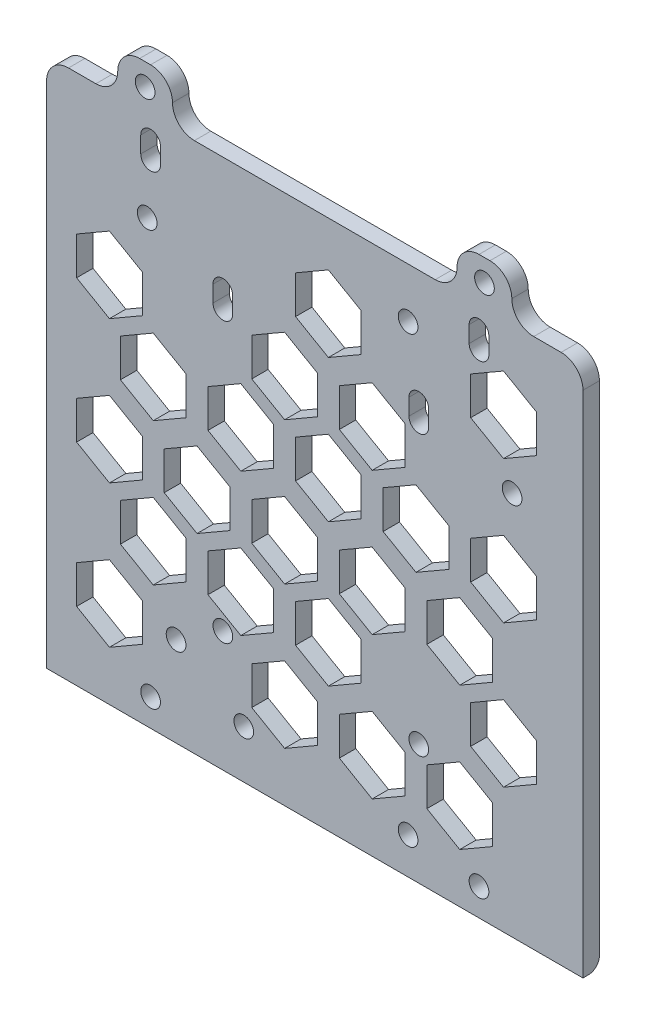
SolidWorks part; units mm, degrees
material "PLA 100% Infill"
ref_plane "Front Plane" through (0, 0, 0) normal (0, 0, 1) x (1, 0, 0)
ref_plane "Top Plane" through (0, 0, 0) normal (0, 1, 0) x (1, 0, 0)
ref_plane "Right Plane" through (0, 0, 0) normal (1, 0, 0) x (0, 0, -1)
sketch "Sketch1" plane through (0, 0, 0) normal (0, 0, 1) x (1, 0, 0)
  line L0 (-49, 97) -> (-49, 0) construction
  line L1 (0, 0) -> (-98, 0)
  line L2 (0, 0) -> (0, 97)
  line L3 (0, 97) -> (-98, 97)
  line L4 (-98, 0) -> (-98, 97)
  line L5 (-80, 101) -> (-18, 101) construction
  line L6 (-98, 97) -> (-75, 97)
  line L8 (-85, 105) -> (-75, 105)
  line L9 (-75, 97) -> (-75, 105)
  line L10 (0, 97) -> (-23, 97)
  line L12 (-13, 105) -> (-23, 105)
  line L13 (-23, 97) -> (-23, 105)
  line L14 (-80, 105) -> (-80, 101) construction
  line L15 (-85, 105) -> (-85, 97)
  line L16 (-80.8, 93) -> (-80.8, 90)
  line L17 (-13, 105) -> (-13, 97)
  line L18 (-18, 105) -> (-18, 101) construction
  line L19 (-77.2, 90) -> (-77.2, 93)
  line L20 (-20.8, 90) -> (-20.8, 93)
  line L21 (-17.2, 93) -> (-17.2, 90)
  line L22 (-19, 91.5) -> (-19, 5) construction
  line L23 (-30, 22) -> (-65.8, 22) construction
  line L24 (-65.8, 76) -> (-65.8, 22) construction
  line L25 (-30, 76) -> (-30, 22) construction
  line L26 (-67.6, 76) -> (-67.6, 73)
  line L27 (-64, 76) -> (-64, 73)
  line L28 (-31.8, 76) -> (-31.8, 73)
  line L29 (-28.2, 76) -> (-28.2, 73)
  circle A0 centre (-79, 5) radius 1.8
  circle A1 centre (-19, 5) radius 1.8
  circle A2 centre (-19, 91.5) radius 1.8
  circle A3 centre (-79, 91.5) radius 1.8
  circle A4 centre (-80, 101) radius 1.8
  circle A5 centre (-18, 101) radius 1.8
  arc A6 (-80.8, 90) -> (-77.2, 90) centre (-79, 90) ccw
  arc A7 (-77.2, 93) -> (-80.8, 93) centre (-79, 93) ccw
  arc A8 (-17.2, 90) -> (-20.8, 90) centre (-19, 90) cw
  arc A9 (-20.8, 93) -> (-17.2, 93) centre (-19, 93) cw
  circle A10 centre (-30, 22) radius 1.8
  circle A11 centre (-65.8, 22) radius 1.8
  circle A12 centre (-65.8, 76) radius 1.8
  circle A13 centre (-30, 76) radius 1.8
  circle A14 centre (-65.8, 73) radius 1.8
  circle A15 centre (-30, 73) radius 1.8
  dimension "D5" = 3.6
  dimension "D8" = 86.5
  dimension "D9" = 10
  dimension "D10" = 8
  dimension "D4" = 5
  dimension "D11" = 62
  dimension "D12" = 62
  dimension "D15" = 4
  dimension "D16" = 60
  dimension "D17" = 3.6
  dimension "D1" = 98
  dimension "D2" = 97
  dimension "D3" = 60
  dimension "D13" = 1.5
  dimension "D14" = 3
  dimension "D18" = 35.8
  dimension "D19" = 30
  dimension "D20" = 22
  dimension "D22" = 3
  dimension "D23" = 54
  dimension "D6" = 2
  dimension "D7" = 2
  dimension "D21" = 2
extrude "Boss-Extrude1" add sketch "Sketch1" along normal blind 3 contours L3 L9 L8 A4 | L4 L1 L2 L3 A3 A2 A1 A0 | L13 L3 L12 A5 region at (-49.0073, 48.3433, 0) region at (-18, 97.1281, 0) region at (-84.8719, 101, 0)
fillet "Fillet1" radius 4 10 edges at (0, 97, 1.5) (-13, 97, 1.5) (-13, 105, 1.5) (-23, 105, 1.5) (-23, 97, 1.5) (-75, 97, 1.5) (-75, 105, 1.5) (-98, 97, 1.5) (-85, 105, 1.5) (-85, 97, 1.5)
fillet "Fillet2" radius 2 1 edges at (-49, 0, 0)
sketch "Sketch3" plane through (0, 0, 3) normal (0, 0, 1) x (1, 0, 0)
  line L0 (-98, 0) -> (-98, 93) construction
  line L1 (-80.5172, 12.537) -> (-80.5172, 19.4652)
  line L2 (-80.5172, 19.4652) -> (-86.5172, 22.9293)
  line L3 (-86.5172, 22.9293) -> (-92.5172, 19.4652)
  line L4 (-92.5172, 19.4652) -> (-92.5172, 12.537)
  line L5 (-92.5172, 12.537) -> (-86.5172, 9.0729)
  line L6 (-86.5172, 9.0729) -> (-80.5172, 12.537)
  line L14 (-72.5172, 26.3934) -> (-72.5172, 33.3216)
  line L15 (-72.5172, 33.3216) -> (-78.5172, 36.7857)
  line L16 (-78.5172, 36.7857) -> (-84.5172, 33.3216)
  line L17 (-84.5172, 33.3216) -> (-84.5172, 26.3934)
  line L18 (-84.5172, 26.3934) -> (-78.5172, 22.9293)
  line L19 (-78.5172, 22.9293) -> (-72.5172, 26.3934)
  line L25 (-56.5172, 26.3934) -> (-56.5172, 33.3216)
  line L26 (-56.5172, 33.3216) -> (-62.5172, 36.7857)
  line L27 (-62.5172, 36.7857) -> (-68.5172, 33.3216)
  line L28 (-68.5172, 33.3216) -> (-68.5172, 26.3934)
  line L29 (-68.5172, 26.3934) -> (-62.5172, 22.9293)
  line L30 (-62.5172, 22.9293) -> (-56.5172, 26.3934)
  line L31 (-48.5172, 12.537) -> (-48.5172, 19.4652)
  line L32 (-48.5172, 19.4652) -> (-54.5172, 22.9293)
  line L33 (-54.5172, 22.9293) -> (-60.5172, 19.4652)
  line L34 (-60.5172, 19.4652) -> (-60.5172, 12.537)
  line L35 (-60.5172, 12.537) -> (-54.5172, 9.0729)
  line L36 (-54.5172, 9.0729) -> (-48.5172, 12.537)
  line L37 (-40.5172, 26.3934) -> (-40.5172, 33.3216)
  line L38 (-40.5172, 33.3216) -> (-46.5172, 36.7857)
  line L39 (-46.5172, 36.7857) -> (-52.5172, 33.3216)
  line L40 (-52.5172, 33.3216) -> (-52.5172, 26.3934)
  line L41 (-52.5172, 26.3934) -> (-46.5172, 22.9293)
  line L42 (-46.5172, 22.9293) -> (-40.5172, 26.3934)
  line L43 (-32.5172, 12.537) -> (-32.5172, 19.4652)
  line L44 (-32.5172, 19.4652) -> (-38.5172, 22.9293)
  line L45 (-38.5172, 22.9293) -> (-44.5172, 19.4652)
  line L46 (-44.5172, 19.4652) -> (-44.5172, 12.537)
  line L47 (-44.5172, 12.537) -> (-38.5172, 9.0729)
  line L48 (-38.5172, 9.0729) -> (-32.5172, 12.537)
  line L55 (-16.5172, 12.537) -> (-16.5172, 19.4652)
  line L56 (-16.5172, 19.4652) -> (-22.5172, 22.9293)
  line L57 (-22.5172, 22.9293) -> (-28.5172, 19.4652)
  line L58 (-28.5172, 19.4652) -> (-28.5172, 12.537)
  line L59 (-28.5172, 12.537) -> (-22.5172, 9.0729)
  line L60 (-22.5172, 9.0729) -> (-16.5172, 12.537)
  line L61 (-8.5172, 26.3934) -> (-8.5172, 33.3216)
  line L62 (-8.5172, 33.3216) -> (-14.5172, 36.7857)
  line L63 (-14.5172, 36.7857) -> (-20.5172, 33.3216)
  line L64 (-20.5172, 33.3216) -> (-20.5172, 26.3934)
  line L65 (-20.5172, 26.3934) -> (-14.5172, 22.9293)
  line L66 (-14.5172, 22.9293) -> (-8.5172, 26.3934)
  line L67 (-64.5172, 38.537) -> (-64.5172, 45.4652)
  line L68 (-64.5172, 45.4652) -> (-70.5172, 48.9293)
  line L69 (-70.5172, 48.9293) -> (-76.5172, 45.4652)
  line L70 (-76.5172, 45.4652) -> (-76.5172, 38.537)
  line L71 (-76.5172, 38.537) -> (-70.5172, 35.0729)
  line L72 (-70.5172, 35.0729) -> (-64.5172, 38.537)
  line L73 (-56.5172, 52.3934) -> (-56.5172, 59.3216)
  line L74 (-56.5172, 59.3216) -> (-62.5172, 62.7857)
  line L75 (-62.5172, 62.7857) -> (-68.5172, 59.3216)
  line L76 (-68.5172, 59.3216) -> (-68.5172, 52.3934)
  line L77 (-68.5172, 52.3934) -> (-62.5172, 48.9293)
  line L78 (-62.5172, 48.9293) -> (-56.5172, 52.3934)
  line L79 (-48.5172, 38.537) -> (-48.5172, 45.4652)
  line L80 (-48.5172, 45.4652) -> (-54.5172, 48.9293)
  line L81 (-54.5172, 48.9293) -> (-60.5172, 45.4652)
  line L82 (-60.5172, 45.4652) -> (-60.5172, 38.537)
  line L83 (-60.5172, 38.537) -> (-54.5172, 35.0729)
  line L84 (-54.5172, 35.0729) -> (-48.5172, 38.537)
  line L85 (-40.5172, 52.3934) -> (-40.5172, 59.3216)
  line L86 (-40.5172, 59.3216) -> (-46.5172, 62.7857)
  line L87 (-46.5172, 62.7857) -> (-52.5172, 59.3216)
  line L88 (-52.5172, 59.3216) -> (-52.5172, 52.3934)
  line L89 (-52.5172, 52.3934) -> (-46.5172, 48.9293)
  line L90 (-46.5172, 48.9293) -> (-40.5172, 52.3934)
  line L91 (-32.5172, 38.537) -> (-32.5172, 45.4652)
  line L92 (-32.5172, 45.4652) -> (-38.5172, 48.9293)
  line L93 (-38.5172, 48.9293) -> (-44.5172, 45.4652)
  line L94 (-44.5172, 45.4652) -> (-44.5172, 38.537)
  line L95 (-44.5172, 38.537) -> (-38.5172, 35.0729)
  line L96 (-38.5172, 35.0729) -> (-32.5172, 38.537)
  line L97 (-24.5172, 52.3934) -> (-24.5172, 59.3216)
  line L98 (-24.5172, 59.3216) -> (-30.5172, 62.7857)
  line L99 (-30.5172, 62.7857) -> (-36.5172, 59.3216)
  line L100 (-36.5172, 59.3216) -> (-36.5172, 52.3934)
  line L101 (-36.5172, 52.3934) -> (-30.5172, 48.9293)
  line L102 (-30.5172, 48.9293) -> (-24.5172, 52.3934)
  line L103 (-16.5172, 38.537) -> (-16.5172, 45.4652)
  line L104 (-16.5172, 45.4652) -> (-22.5172, 48.9293)
  line L105 (-22.5172, 48.9293) -> (-28.5172, 45.4652)
  line L106 (-28.5172, 45.4652) -> (-28.5172, 38.537)
  line L107 (-28.5172, 38.537) -> (-22.5172, 35.0729)
  line L108 (-22.5172, 35.0729) -> (-16.5172, 38.537)
  line L109 (-8.5172, 52.3934) -> (-8.5172, 59.3216)
  line L110 (-8.5172, 59.3216) -> (-14.5172, 62.7857)
  line L111 (-14.5172, 62.7857) -> (-20.5172, 59.3216)
  line L112 (-20.5172, 59.3216) -> (-20.5172, 52.3934)
  line L113 (-20.5172, 52.3934) -> (-14.5172, 48.9293)
  line L114 (-14.5172, 48.9293) -> (-8.5172, 52.3934)
  line L127 (-48.5172, 64.537) -> (-48.5172, 71.4652)
  line L128 (-48.5172, 71.4652) -> (-54.5172, 74.9293)
  line L129 (-54.5172, 74.9293) -> (-60.5172, 71.4652)
  line L130 (-60.5172, 71.4652) -> (-60.5172, 64.537)
  line L131 (-60.5172, 64.537) -> (-54.5172, 61.0729)
  line L132 (-54.5172, 61.0729) -> (-48.5172, 64.537)
  line L133 (-40.5172, 78.3934) -> (-40.5172, 85.3216)
  line L134 (-40.5172, 85.3216) -> (-46.5172, 88.7857)
  line L135 (-46.5172, 88.7857) -> (-52.5172, 85.3216)
  line L136 (-52.5172, 85.3216) -> (-52.5172, 78.3934)
  line L137 (-52.5172, 78.3934) -> (-46.5172, 74.9293)
  line L138 (-46.5172, 74.9293) -> (-40.5172, 78.3934)
  line L139 (-32.5172, 64.537) -> (-32.5172, 71.4652)
  line L140 (-32.5172, 71.4652) -> (-38.5172, 74.9293)
  line L141 (-38.5172, 74.9293) -> (-44.5172, 71.4652)
  line L142 (-44.5172, 71.4652) -> (-44.5172, 64.537)
  line L143 (-44.5172, 64.537) -> (-38.5172, 61.0729)
  line L144 (-38.5172, 61.0729) -> (-32.5172, 64.537)
  line L157 (-8.5172, 78.3934) -> (-8.5172, 85.3216)
  line L158 (-8.5172, 85.3216) -> (-14.5172, 88.7857)
  line L159 (-14.5172, 88.7857) -> (-20.5172, 85.3216)
  line L160 (-20.5172, 85.3216) -> (-20.5172, 78.3934)
  line L161 (-20.5172, 78.3934) -> (-14.5172, 74.9293)
  line L162 (-14.5172, 74.9293) -> (-8.5172, 78.3934)
  line L163 (-80.5172, 38.537) -> (-80.5172, 45.4652)
  line L164 (-80.5172, 45.4652) -> (-86.5172, 48.9293)
  line L165 (-86.5172, 48.9293) -> (-92.5172, 45.4652)
  line L166 (-92.5172, 45.4652) -> (-92.5172, 38.537)
  line L167 (-92.5172, 38.537) -> (-86.5172, 35.0729)
  line L168 (-86.5172, 35.0729) -> (-80.5172, 38.537)
  line L169 (-72.5172, 52.3934) -> (-72.5172, 59.3216)
  line L170 (-72.5172, 59.3216) -> (-78.5172, 62.7857)
  line L171 (-78.5172, 62.7857) -> (-84.5172, 59.3216)
  line L172 (-84.5172, 59.3216) -> (-84.5172, 52.3934)
  line L173 (-84.5172, 52.3934) -> (-78.5172, 48.9293)
  line L174 (-78.5172, 48.9293) -> (-72.5172, 52.3934)
  line L175 (-80.5172, 64.537) -> (-80.5172, 71.4652)
  line L176 (-80.5172, 71.4652) -> (-86.5172, 74.9293)
  line L177 (-86.5172, 74.9293) -> (-92.5172, 71.4652)
  line L178 (-92.5172, 71.4652) -> (-92.5172, 64.537)
  line L179 (-92.5172, 64.537) -> (-86.5172, 61.0729)
  line L180 (-86.5172, 61.0729) -> (-80.5172, 64.537)
  line L187 (-56.5172, 85.3216) -> (-62.5172, 88.7857) [skipped]
  line L188 (-68.5172, 78.3934) -> (-62.5172, 74.9293) [skipped]
  line L189 (-64.5172, 71.4652) -> (-70.5172, 74.9293) [skipped]
  line L190 (-76.5172, 64.537) -> (-70.5172, 61.0729) [skipped]
  line L191 (-70.5172, 61.0729) -> (-64.5172, 64.537) [skipped]
  line L192 (-64.5172, 64.537) -> (-64.5172, 71.4652) [skipped]
  line L193 (-70.5172, 74.9293) -> (-76.5172, 71.4652) [skipped]
  line L194 (-76.5172, 71.4652) -> (-76.5172, 64.537) [skipped]
  line L195 (-62.5172, 88.7857) -> (-68.5172, 85.3216) [skipped]
  line L196 (-72.5172, 78.3934) -> (-72.5172, 85.3216) [skipped]
  line L197 (-84.5172, 85.3216) -> (-84.5172, 78.3934) [skipped]
  line L198 (-78.5172, 88.7857) -> (-84.5172, 85.3216) [skipped]
  line L199 (-72.5172, 85.3216) -> (-78.5172, 88.7857) [skipped]
  line L200 (-84.5172, 78.3934) -> (-78.5172, 74.9293) [skipped]
  line L201 (-78.5172, 74.9293) -> (-72.5172, 78.3934) [skipped]
  line L202 (-68.5172, 85.3216) -> (-68.5172, 78.3934) [skipped]
  line L203 (-62.5172, 74.9293) -> (-56.5172, 78.3934) [skipped]
  line L204 (-56.5172, 78.3934) -> (-56.5172, 85.3216) [skipped]
  line L205 (-36.5172, 78.3934) -> (-30.5172, 74.9293) [skipped]
  line L206 (-24.5172, 78.3934) -> (-24.5172, 85.3216) [skipped]
  line L207 (-30.5172, 88.7857) -> (-36.5172, 85.3216) [skipped]
  line L208 (-36.5172, 85.3216) -> (-36.5172, 78.3934) [skipped]
  line L209 (-24.5172, 85.3216) -> (-30.5172, 88.7857) [skipped]
  line L210 (-30.5172, 74.9293) -> (-24.5172, 78.3934) [skipped]
  line L211 (-64.5172, 19.4652) -> (-70.5172, 22.9293) [skipped]
  line L212 (-64.5172, 12.537) -> (-64.5172, 19.4652) [skipped]
  line L213 (-36.5172, 26.3934) -> (-30.5172, 22.9293) [skipped]
  line L214 (-30.5172, 22.9293) -> (-24.5172, 26.3934) [skipped]
  line L215 (-24.5172, 23.3102) -> (-24.5172, 33.3216) [skipped]
  line L216 (-24.5172, 33.3216) -> (-30.5172, 36.7857) [skipped]
  line L217 (-30.5172, 36.7857) -> (-36.5172, 33.3216) [skipped]
  line L218 (-36.5172, 33.3216) -> (-36.5172, 26.3934) [skipped]
  line L219 (-70.5172, 9.0729) -> (-64.5172, 12.537) [skipped]
  line L220 (-76.5172, 12.537) -> (-70.5172, 9.0729) [skipped]
  line L221 (-76.5172, 19.4652) -> (-76.5172, 12.537) [skipped]
  line L222 (-70.5172, 22.9293) -> (-76.5172, 19.4652) [skipped]
  line L223 (-22.5172, 74.9293) -> (-28.5172, 71.4652) [skipped]
  line L224 (-28.5172, 71.4652) -> (-28.5172, 64.537) [skipped]
  line L225 (-22.5172, 61.0729) -> (-16.5172, 64.537) [skipped]
  line L226 (-16.5172, 64.537) -> (-16.5172, 71.4652) [skipped]
  line L227 (-16.5172, 71.4652) -> (-22.5172, 74.9293) [skipped]
  line L228 (-28.5172, 64.537) -> (-22.5172, 61.0729) [skipped]
  circle A0 centre (-86.5172, 16.0011) radius 6 construction
  circle A2 centre (-78.5172, 29.8575) radius 6 construction
  point P10 (-75.5172, 24.6614)
  dimension "D1" = 12
  dimension "D2" = 12
  dimension "D3" = 4
  dimension "D4" = 2
  dimension "D5" = 5
  dimension "D6" = 3
extrude "Cut-Extrude1" cut sketch "Sketch3" against normal through all
sketch "Sketch4" plane through (0, 0, 3) normal (0, 0, 1) x (1, 0, 0)
  circle A0 centre (-74.3438, 16.37) radius 1.8
  circle A1 centre (-61.9736, 8.8272) radius 1.8
  circle A2 centre (-31.9533, 6.6831) radius 1.8
  circle A3 centre (-12.9454, 70.2256) radius 1.8
  circle A4 centre (-31.9533, 87.8757) radius 1.8
  circle A5 centre (-79.6238, 80.4838) radius 1.8
  dimension "D1" = 3.6
extrude "Cut-Extrude2" cut sketch "Sketch4" against normal through all
